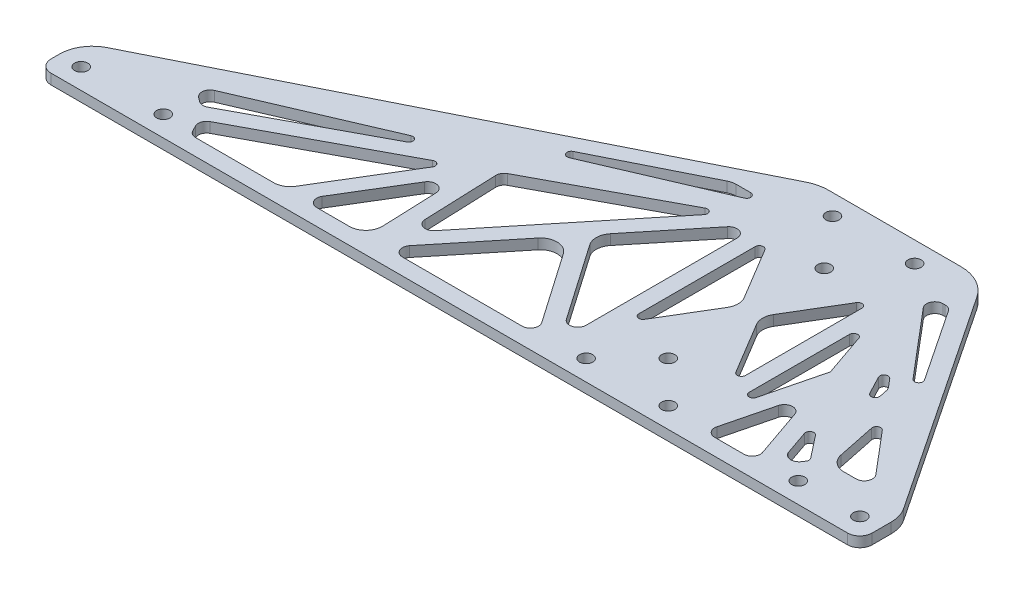
SolidWorks part; units mm, degrees
ref_plane "Front Plane" through (0, 0, 0) normal (0, 0, 1) x (1, 0, 0)
ref_plane "Top Plane" through (0, 0, 0) normal (0, 1, 0) x (1, 0, 0)
ref_plane "Right Plane" through (0, 0, 0) normal (1, 0, 0) x (0, 0, -1)
sketch "Sketch1" plane through (0, 0, 0) normal (0, 1, 0) x (1, 0, 0)
  line L0 (0, 0) -> (254, 0)
  line L2 (203.2, 88.9) -> (152.4, 88.9)
  line L4 (0, 0) -> (0, 12.7)
  line L5 (0, 12.7) -> (152.4, 88.9)
  line L6 (203.2, 88.9) -> (254, 12.7)
  line L7 (254, 12.7) -> (254, 0)
  line L8 (0, 6.35) -> (41.2306, 6.35) construction
  line L9 (254, 6.35) -> (220.1675, 6.35) construction
  line L10 (139.7, 82.55) -> (207.4333, 82.55) construction
  line L11 (156.6333, 76.2) -> (38.0113, 12.7) construction
  line L12 (38.0113, 12.7) -> (22.7185, 24.0592)
  line L13 (226.5259, 15.8112) -> (251.9259, 15.8112)
  line L20 (127, 76.2) -> (211.6667, 76.2)
  line L21 (226.5259, 15.8112) -> (215.9, 0)
  line L22 (38.0113, 12.7) -> (44.45, 0)
  line L23 (156.6333, 76.2) -> (27.2885, 20.6647) construction
  line L24 (156.6333, 76.2) -> (98.8302, 5.08) construction
  line L28 (194.7333, 76.2) -> (226.5259, 15.8112) construction
  line L31 (5.08, 9.5604) -> (153.5992, 83.82)
  line L32 (200.4813, 83.82) -> (153.5992, 83.82)
  line L33 (200.4813, 83.82) -> (248.92, 11.1619)
  line L34 (248.92, 11.1619) -> (248.92, 5.08)
  line L35 (5.08, 5.08) -> (248.92, 5.08)
  line L36 (5.08, 5.08) -> (5.08, 9.5604)
  line L37 (219.314, 5.08) -> (194.7333, 76.2) construction
  line L39 (194.7333, 76.2) -> (245.8205, 15.8112) construction
  line L40 (98.8302, 5.08) -> (97.3223, 44.45) construction
  line L41 (127.7318, 40.64) -> (152.3892, 5.08) construction
  line L42 (207.0237, 40.64) -> (198.1092, 5.08) construction
  line L83 (226.5259, 15.8112) -> (220.2769, 46.0056) construction
  line L84 (207.0237, 40.64) -> (226.5259, 15.8112) construction
  line L107 (97.3223, 44.45) -> (73.4302, 5.08) construction
  line L108 (156.6333, 76.2) -> (194.7333, 12.7) construction
  line L113 (194.7333, 76.2) -> (156.6333, 12.7) construction
  line L114 (155.6312, 78.534) -> (26.2864, 22.9986)
  line L115 (155.4346, 78.4393) -> (36.8125, 14.9393)
  line L116 (154.6622, 77.802) -> (101.1104, 11.9127)
  line L117 (156.6333, 12.7) -> (154.0933, 8.1397)
  line L118 (156.6333, 12.7) -> (194.7333, 12.7)
  line L119 (194.7333, 12.7) -> (200.3598, 0)
  line L120 (153.0965, 6.35) -> (197.5465, 6.35) construction
  line L123 (101.1104, 11.9127) -> (99.5369, 52.9951)
  line L124 (99.5369, 52.9951) -> (96.1931, 47.4852)
  line L125 (125.6445, 39.1927) -> (150.3019, 3.6327)
  line L126 (192.5553, 77.5068) -> (154.4553, 14.0068)
  line L127 (154.4553, 74.8932) -> (192.5553, 11.3932)
  line L128 (156.6333, 12.7) -> (156.6333, 76.2) construction
  line L129 (194.7333, 12.7) -> (194.7333, 76.2) construction
  line L130 (197.2733, 12.7) -> (197.2733, 76.2)
  line L131 (159.1733, 12.7) -> (159.1733, 76.2)
  line L132 (192.1933, 12.7) -> (192.1933, 76.2)
  line L133 (154.0933, 12.7) -> (154.0933, 76.2)
  line L134 (205.8201, 46.2844) -> (228.5234, 17.3801)
  line L137 (205.8201, 46.2844) -> (195.6454, 5.6976)
  line L138 (221.7147, 5.9097) -> (197.134, 77.0297)
  line L139 (192.4858, 75.0167) -> (224.2783, 14.6279)
  line L140 (229.0132, 16.3259) -> (222.7642, 46.5203)
  line L141 (157.6354, 73.866) -> (28.2906, 18.3307)
  line L142 (157.8321, 73.9607) -> (39.21, 10.4607)
  line L143 (158.6044, 74.598) -> (96.5501, -1.7527)
  line L144 (96.5501, -1.7527) -> (95.1077, 35.9049)
  line L145 (95.1077, 35.9049) -> (75.6017, 3.7622)
  line L146 (129.8191, 42.0873) -> (154.4765, 6.5273)
  line L147 (196.9114, 74.8932) -> (158.8114, 11.3932)
  line L148 (158.8114, 77.5068) -> (196.9114, 14.0068)
  line L149 (208.2273, 34.9956) -> (224.5284, 14.2422)
  line L150 (208.2273, 34.9956) -> (200.5729, 4.4624)
  line L151 (216.9134, 4.2503) -> (192.3327, 75.3703)
  line L152 (196.9809, 77.3833) -> (228.7734, 16.9944)
  line L153 (224.0386, 15.2964) -> (217.7896, 45.4908)
  line L154 (71.2588, 6.3978) -> (70.4591, 5.08)
  line L155 (36.8125, 14.9393) -> (35.7571, 14.3744)
  line L156 (39.21, 10.4607) -> (39.1601, 10.434)
  line L157 (154.0933, 12.7) -> (154.0933, 7.0799)
  line L158 (197.2733, 12.7) -> (197.2733, 6.9667)
  line L159 (224.5284, 14.2422) -> (225.0366, 13.5952)
  line L160 (229.0132, 16.3259) -> (229.1197, 15.8112)
  line L161 (192.7942, 74.5595) -> (243.8813, 14.1707)
  line L162 (196.6725, 77.8405) -> (247.7597, 17.4517)
  line L163 (153.766, 7.552) -> (149.5598, 0)
  line L164 (95.5112, 46.3615) -> (71.2588, 6.3978)
  line L165 (99.5369, 52.9951) -> (71.2588, 6.3978) construction
  line L166 (175.6833, 19.05) -> (162.9833, 6.35) construction
  line L167 (175.6833, 19.05) -> (188.3833, 6.35) construction
  line L168 (162.9833, 82.55) -> (175.6833, 67.31) construction
  line L169 (175.6833, 67.31) -> (188.3833, 82.55) construction
  circle A0 centre (6.7733, 6.35) radius 2.032
  circle A1 centre (32.1733, 6.35) radius 2.032
  circle A2 centre (228.6, 6.35) radius 2.032
  circle A3 centre (247.65, 6.35) radius 2.032
  circle A4 centre (162.9833, 82.55) radius 2.032
  circle A5 centre (188.3833, 82.55) radius 2.032
  circle A28 centre (162.9833, 6.35) radius 2.032
  circle A29 centre (188.3833, 6.35) radius 2.032
  arc A32 (197.2733, 12.7) -> (192.1933, 12.7) centre (194.7333, 12.7) cw
  arc A33 (197.2733, 76.2) -> (192.1933, 76.2) centre (194.7333, 76.2) ccw
  arc A34 (159.1733, 12.7) -> (154.0933, 12.7) centre (156.6333, 12.7) cw
  arc A35 (159.1733, 76.2) -> (154.0933, 76.2) centre (156.6333, 76.2) ccw
  arc A37 (155.6312, 78.534) -> (157.6354, 73.866) centre (156.6333, 76.2) cw
  arc A38 (26.2864, 22.9986) -> (28.2906, 18.3307) centre (27.2885, 20.6647) ccw
  arc A39 (155.4346, 78.4393) -> (157.8321, 73.9607) centre (156.6333, 76.2) cw
  arc A40 (36.8125, 14.9393) -> (39.21, 10.4607) centre (38.0113, 12.7) ccw
  arc A41 (154.6622, 77.802) -> (158.6044, 74.598) centre (156.6333, 76.2) cw
  arc A42 (71.2588, 6.3978) -> (75.6017, 3.7622) centre (73.4302, 5.08) ccw
  arc A43 (125.6445, 39.1927) -> (129.8191, 42.0873) centre (127.7318, 40.64) cw
  arc A44 (150.3019, 3.6327) -> (154.4765, 6.5273) centre (152.3892, 5.08) ccw
  arc A45 (192.5553, 77.5068) -> (196.9114, 74.8932) centre (194.7333, 76.2) cw
  arc A46 (154.4553, 14.0068) -> (158.8114, 11.3932) centre (156.6333, 12.7) ccw
  arc A47 (154.4553, 74.8932) -> (158.8114, 77.5068) centre (156.6333, 76.2) cw
  arc A48 (192.5553, 11.3932) -> (196.9114, 14.0068) centre (194.7333, 12.7) ccw
  arc A49 (228.5234, 17.3801) -> (224.5284, 14.2422) centre (226.5259, 15.8112) cw
  arc A50 (195.6454, 5.6976) -> (200.5729, 4.4624) centre (198.1092, 5.08) ccw
  arc A51 (221.7147, 5.9097) -> (216.9134, 4.2503) centre (219.314, 5.08) cw
  arc A52 (197.134, 77.0297) -> (192.3327, 75.3703) centre (194.7333, 76.2) ccw
  arc A53 (192.4858, 75.0167) -> (196.9809, 77.3833) centre (194.7333, 76.2) cw
  arc A54 (224.2783, 14.6279) -> (228.7734, 16.9944) centre (226.5259, 15.8112) ccw
  arc A55 (229.0132, 16.3259) -> (224.0386, 15.2964) centre (226.5259, 15.8112) cw
  arc A56 (222.7642, 46.5203) -> (217.7896, 45.4908) centre (220.2769, 46.0056) ccw
  arc A57 (192.7942, 74.5595) -> (196.6725, 77.8405) centre (194.7333, 76.2) cw
  arc A58 (243.8813, 14.1707) -> (247.7597, 17.4517) centre (245.8205, 15.8112) ccw
  circle A59 centre (175.6833, 19.05) radius 2.032
  circle A60 centre (175.6833, 67.31) radius 2.032
  dimension "D7" = 4.064
  dimension "D8" = 25.4
  dimension "D9" = 130.81
  dimension "D10" = 19.05
  dimension "D11" = 6.35
  dimension "D13" = 19.05
  dimension "D1" = 254
  dimension "D2" = 50.8
  dimension "D3" = 88.9
  dimension "D4" = 152.4
  dimension "D5" = 12.7
  dimension "D6" = 6.35
  dimension "D12" = 25.4
  dimension "D14" = 44.45
  dimension "D15" = 19.05
  dimension "D16" = 25.4
  dimension "D18" = 12.7
  dimension "D19" = 38.1
  dimension "D20" = 19.05
  dimension "D21" = 12.7
  dimension "D22" = 25.4
  dimension "D23" = 50.8
  dimension "D24" = 25.4
  dimension "D29" = 6.35
  dimension "D30" = 38.1
  dimension "D31" = 25.4
  dimension "D32" = 6.35
  dimension "D33" = 2.54
  dimension "D34" = 50.8
  dimension "D35" = 7.552
  dimension "D36" = 12.7
  dimension "D38" = 15.24
  dimension "D17" = 5.08
  dimension "D25" = 2.54
  dimension "D26" = 2.54
  dimension "D27" = 2.54
  dimension "D28" = 2.54
  dimension "D37" = 2.54
extrude "Boss-Extrude1" add sketch "Sketch1" along normal blind 3.175 contours L0 L7 L6 L2 L5 L4 | A0 | A1 | A5 | A4 | A2 | A3
extrude "Cut-Extrude2" cut sketch "Sketch1<3>" along normal through all contours L142 L156 L22 L35 L154 L124 | L155 L115 L124 L141 L12 | L144 L145 L35 | L116 L142 L123 | L125 L143 L35 | L157 L133 L143 L146 L117 | L114 L20 L31 | L130 L158 L137 L151 | L35 L151 L150 | L161 L152 L153 | L161 L140 L160 L13 | L159 L149 L138 L21 | L20 L162 L33 | L131 L126 L127 | L147 L148 L132 | L115 L141 L123 | A28 | A29 | A59 | A60 region at (64.7257, 0, -16.4796) region at (89.2658, 0, -15.355) region at (126.3241, 0, -15.5249) region at (118.3245, 0, -64.21) region at (56.1323, 0, -27.8913) region at (146.3644, 0, -38.8822) region at (115.9087, 0, -40.9571) region at (100.9162, 0, -49.3843) region at (212.3574, 0, -62.2554) region at (208.2553, 0, -13.9673) region at (220.1621, 0, -16.1676) region at (199.6409, 0, -37.9304) region at (163.6893, 0, -44.45) region at (232.1338, 0, -22.7875) region at (215.3763, 0, -44.8583) region at (187.6774, 0, -44.45)
sketch "Sketch1<3>" plane through (0, 0, 0) normal (0, 1, 0) x (1, 0, 0) same geometry as "Sketch1"
fillet "Fillet1" radius 3.81 2 edges at (254, 1.5875, 0) (0, 1.5875, 0)
fillet "Fillet2" radius 10.16 2 edges at (254, 1.5875, -12.7) (0, 1.5875, -12.7)
fillet "Fillet3" radius 12.7 2 edges at (203.2, 1.5875, -88.9) (152.4, 1.5875, -88.9)
fillet "Fillet4" radius 1.27 17 edges at (214.3608, 1.5875, -27.1869) (233.4505, 1.5875, -34.3662) (207.8157, 1.5875, -56.8029) (220.3926, 1.5875, -32.9136) (197.2733, 1.5875, -61.0753) (197.2733, 1.5875, -12.1914) (159.1733, 1.5875, -67.0298) (192.1933, 1.5875, -67.0298) (192.1933, 1.5875, -21.8702) (159.1733, 1.5875, -21.8702) (146.6944, 1.5875, -67.9985) (66.4191, 1.5875, -40.2299) (150.1953, 1.5875, -76.2) (224.7883, 1.5875, -36.74) (103.3533, 1.5875, -50.5595) (90.3319, 1.5875, -37.8269) (225.0366, 1.5875, -13.5952)
fillet "Fillet5" radius 2.54 20 edges at (39.1601, 1.5875, -10.434) (41.8745, 1.5875, -5.08) (99.9212, 1.5875, -42.9602) (101.1104, 1.5875, -11.9127) (95.1077, 1.5875, -35.9049) (76.4014, 1.5875, -5.08) (35.7571, 1.5875, -14.3744) (29.6468, 1.5875, -18.913) (198.0603, 1.5875, -76.2) (205.5613, 1.5875, -76.2) (217.9205, 1.5875, -44.8583) (242.4935, 1.5875, -15.8112) (221.0887, 1.5875, -7.7208) (216.6266, 1.5875, -5.08) (200.7278, 1.5875, -5.08) (207.4116, 1.5875, -31.7419) (154.0933, 1.5875, -69.0476) (149.2983, 1.5875, -5.08) (102.1034, 1.5875, -5.08) (154.0933, 1.5875, -7.0799)
fillet "Fillet6" radius 5.08 8 edges at (229.1197, 1.5875, -15.8112) (96.2884, 1.5875, -5.08) (172.7212, 1.5875, -44.45) (178.6455, 1.5875, -44.45) (130.9066, 1.5875, -40.519) (127.5708, 1.5875, -36.4147) (138.3592, 1.5875, -76.2) (70.4591, 1.5875, -5.08)
